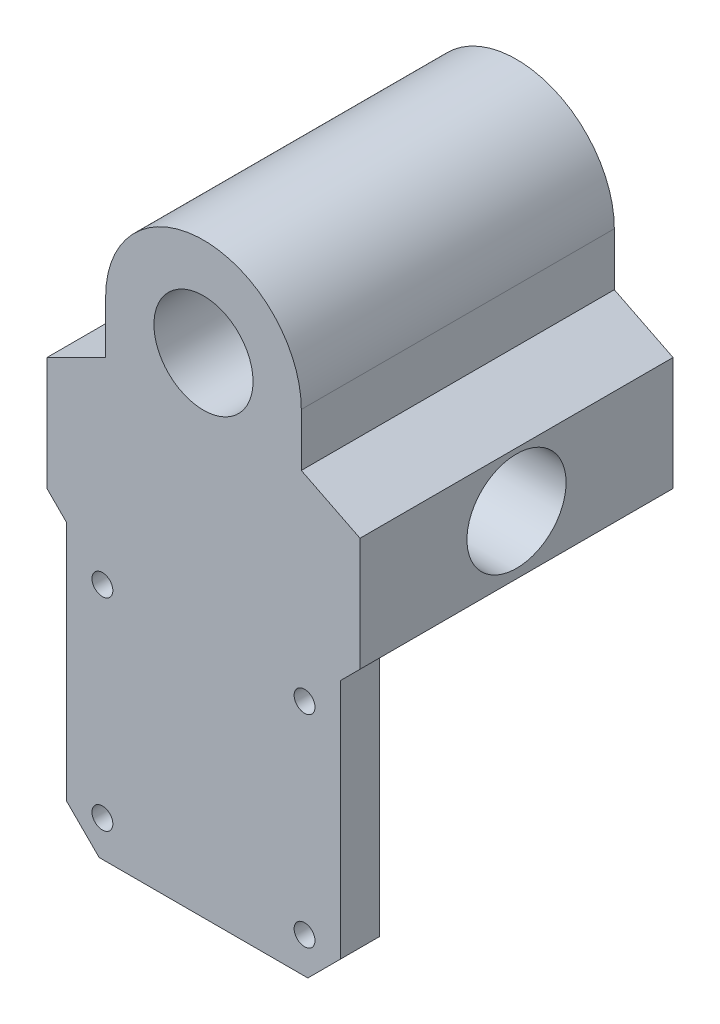
SolidWorks part; units mm, degrees
material "PET"
ref_plane "Front Plane" through (0, 0, 0) normal (0, 0, 1) x (1, 0, 0)
ref_plane "Top Plane" through (0, 0, 0) normal (0, 1, 0) x (1, 0, 0)
ref_plane "Right Plane" through (0, 0, 0) normal (1, 0, 0) x (0, 0, -1)
sketch "Sketch1" plane through (0, 0, 0) normal (0, 1, 0) x (1, 0, 0)
  line L0 (-24, 24) -> (24, -24) construction
  line L1 (-24, -24) -> (24, -24)
  line L2 (-24, -24) -> (-24, 24)
  line L3 (-24, 24) -> (24, 24)
  line L4 (24, -24) -> (24, 24)
  point P4 (0, 0)
  dimension "D1" = 48
  dimension "D2" = 48
extrude "Boss-Extrude1" add sketch "Sketch1" along normal blind 55 and the other way blind 5
sketch "Sketch2" plane through (0, 0, 24) normal (0, 0, 1) x (1, 0, 0)
  line L0 (0, 55) -> (0, 0) construction
  line L1 (-24, 55) -> (24, 55) construction
  circle A0 centre (0, 28) radius 7.6
  dimension "D1" = 15.2
  dimension "D2" = 27
extrude "Cut-Extrude1" cut sketch "Sketch2" against normal through all
sketch "Sketch3" plane through (24, 0, 0) normal (1, 0, 0) x (0, 0, -1)
  line L0 (0, 55) -> (0, 0) construction
  line L1 (-24, 55) -> (24, 55) construction
  circle A0 centre (0, 7) radius 7.6
  dimension "D1" = 15.2
  dimension "D2" = 48
extrude "Cut-Extrude2" cut sketch "Sketch3" against normal through all
sketch "Sketch6" plane through (0, 0, 24) normal (0, 0, 1) x (1, 0, 0)
  line L0 (-24, -5) -> (24, -5) construction
  line L1 (-21, -5) -> (21, -5)
  line L2 (-21, -5) -> (-21, -47)
  line L3 (-21, -47) -> (21, -47)
  line L4 (21, -5) -> (21, -47)
  point P7 (0, -5)
  dimension "D1" = 42
  dimension "D2" = 42
extrude "Boss-Extrude2" add sketch "Sketch6" against normal blind 6
sketch "Sketch7" plane through (0, 0, 18) normal (0, 0, -1) x (-1, 0, 0)
  line L0 (15.5, -41.5) -> (-15.5, -10.5) construction
  line L1 (-21, -5) -> (21, -47) construction
  line L2 (21, -47) -> (-21, -47) construction
  line L3 (21, -5) -> (21, -47) construction
  circle A0 centre (-15.5, -10.5) radius 1.6
  circle A1 centre (-15.5, -41.5) radius 1.6
  circle A2 centre (15.5, -41.5) radius 1.6
  circle A3 centre (15.5, -10.5) radius 1.6
  point P8 (0, -26)
  dimension "D1" = 3.2
  dimension "D2" = 3.2
  dimension "D3" = 3.2
  dimension "D4" = 3.2
  dimension "D5" = 31
  dimension "D6" = 31
extrude "Cut-Extrude4" cut sketch "Sketch7" against normal through all
sketch "Sketch9" plane through (0, 0, -24) normal (0, 0, -1) x (-1, 0, 0)
  line L0 (-1025, 20.4) -> (-15, 20.4) construction
  line L2 (-15, 28) -> (-15, 20.4)
  line L4 (-15, 20.4) -> (-24, 20.4)
  line L6 (-24, 20.4) -> (-24, 55)
  line L7 (-24, 55) -> (24, 55)
  line L8 (24, 55) -> (24, 20.4)
  line L10 (15, 28) -> (15, 20.4)
  line L11 (15, 20.4) -> (24, 20.4)
  line L12 (15, 20.4) -> (1031, 20.4) construction
  arc A0 (15, 28) -> (-15, 28) centre (0, 28) ccw
  circle A1 centre (0, 28) radius 7.6 construction
  line M4 (-24, 55) -> (-24, -5)
  dimension "D1" = 15
extrude "Cut-Extrude5" cut sketch "Sketch9" against normal through all contours A0 L7 L4 L2 M4 region at (15.5917, 24.2, -24)
chamfer "Chamfer12" distance 5 distance2 10 1 edges at (24, 20.4, 0) first distance on face at (24, 7, -7.6)
chamfer "Chamfer13" distance 10 distance2 5 1 edges at (-24, 20.4, 0) first distance on face at (-19.5, 20.4, 0)
chamfer "Chamfer14" distance 3 angle 45 2 edges at (-24, -5, 0) (24, -5, 0)
chamfer "Chamfer15" distance 5 angle 45 2 edges at (-21, -47, 21) (21, -47, 21)
equation "\"tolerance\"=0.2"
equation "\"D1@Sketch2\"=\"tolerance\"+15"
equation "\"D1@Sketch3\"=\"tolerance\"+15"
